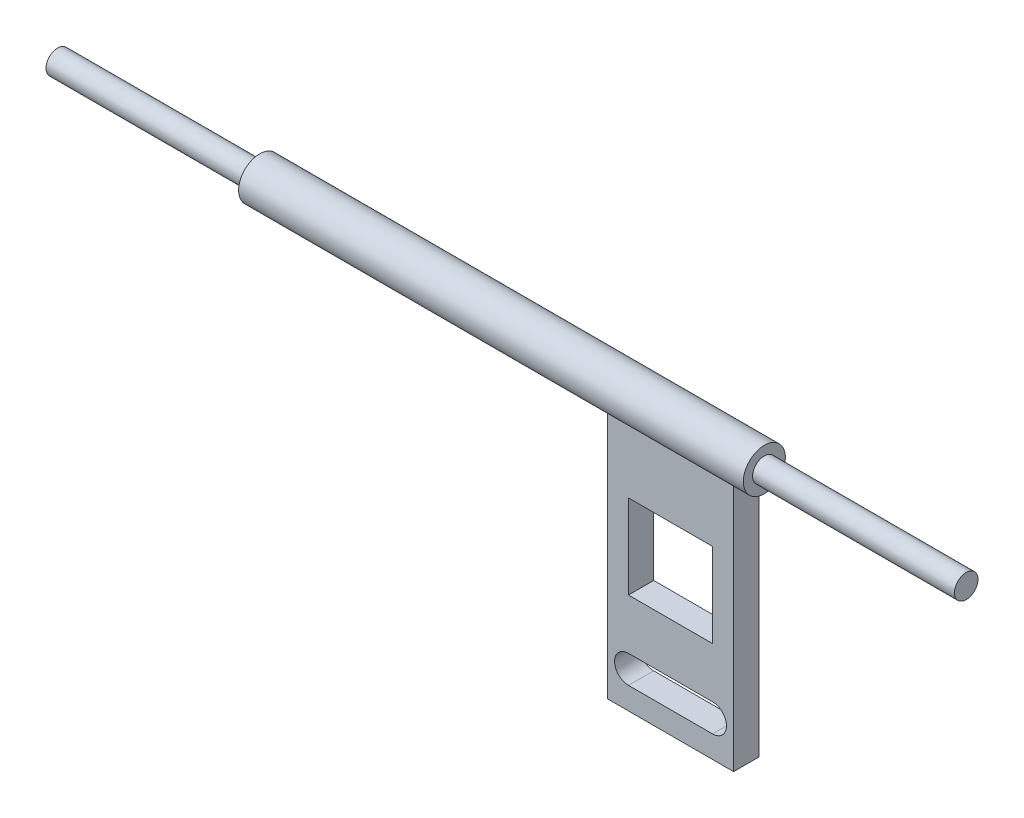
SolidWorks part; units mm, degrees
ref_plane "Front Plane" through (0, 0, 0) normal (0, 0, 1) x (1, 0, 0)
ref_plane "Top Plane" through (0, 0, 0) normal (0, 1, 0) x (1, 0, 0)
ref_plane "Right Plane" through (0, 0, 0) normal (1, 0, 0) x (0, 0, -1)
sketch "Sketch1" plane through (0, 0, 0) normal (1, 0, 0) x (0, 0, -1)
  circle A0 centre (0, 0) radius 1.4
  dimension "D1" = 2.8
extrude "Boss-Extrude1" add sketch "Sketch1" along normal blind 24
sketch "Sketch2" plane through (24, 0, 0) normal (1, 0, 0) x (0, 0, -1)
  circle A0 centre (0, 0) radius 2.5
  dimension "D1" = 5
extrude "Boss-Extrude2" add sketch "Sketch2" along normal blind 60
sketch "Sketch3" plane through (84, 0, 0) normal (1, 0, 0) x (0, 0, -1)
  circle A0 centre (0, 0) radius 1.4
  dimension "D1" = 2.8
extrude "Boss-Extrude3" add sketch "Sketch3" along normal blind 24
sketch "Sketch4" plane through (0, 0, 0) normal (0, 0, 1) x (1, 0, 0)
  line L0 (84, -2.5) -> (84, 2.5) construction
  line L1 (66.8461, -1.4351) -> (81.8461, -1.4351)
  line L2 (66.8461, -1.4351) -> (66.8461, -31.4351)
  line L3 (66.8461, -31.4351) -> (81.8461, -31.4351)
  line L4 (81.8461, -1.4351) -> (81.8461, -31.4351)
  dimension "D1" = 30
  dimension "D2" = 15
  dimension "D3" = 2.1539
extrude "Boss-Extrude4" add sketch "Sketch4" along normal blind 1.5 and the other way blind 1.5
sketch "Sketch5" plane through (0, 0, -1.5) normal (0, 0, -1) x (-1, 0, 0)
  line L0 (-66.8461, -2.5) -> (-24, -2.5) construction
  line L1 (-79.3461, -9.5) -> (-69.3461, -9.5)
  line L2 (-79.3461, -9.5) -> (-79.3461, -19.5)
  line L3 (-79.3461, -19.5) -> (-69.3461, -19.5)
  line L4 (-69.3461, -9.5) -> (-69.3461, -19.5)
  line L5 (-74.3461, -2) -> (-74.3461, -25.5) construction
  line L6 (-66.8461, -2) -> (-81.8461, -2) construction
  line L7 (-79.3461, -25.5) -> (-69.3461, -25.5)
  line L8 (-79.3461, -28.8) -> (-69.3461, -28.8)
  line L9 (-74.3461, -28.8) -> (-74.3461, -29.2308) construction
  line L10 (-66.8461, -2.5) -> (-24, -2.5) construction
  arc A0 (-79.3461, -25.5) -> (-79.3461, -28.8) centre (-79.3461, -27.15) ccw
  arc A1 (-69.3461, -25.5) -> (-69.3461, -28.8) centre (-69.3461, -27.15) cw
  dimension "D3" = 3.3
  dimension "D1" = 7
  dimension "D2" = 10
  dimension "D4" = 23
  dimension "D5" = 10
  dimension "D6" = 5
  dimension "D7" = 10
extrude "Cut-Extrude1" cut sketch "Sketch5" against normal blind 7 and the other way blind 10
ref_plane "Plane1" through (5, 0, 0) normal (1, 0, 0) x (0, 0, -1)
